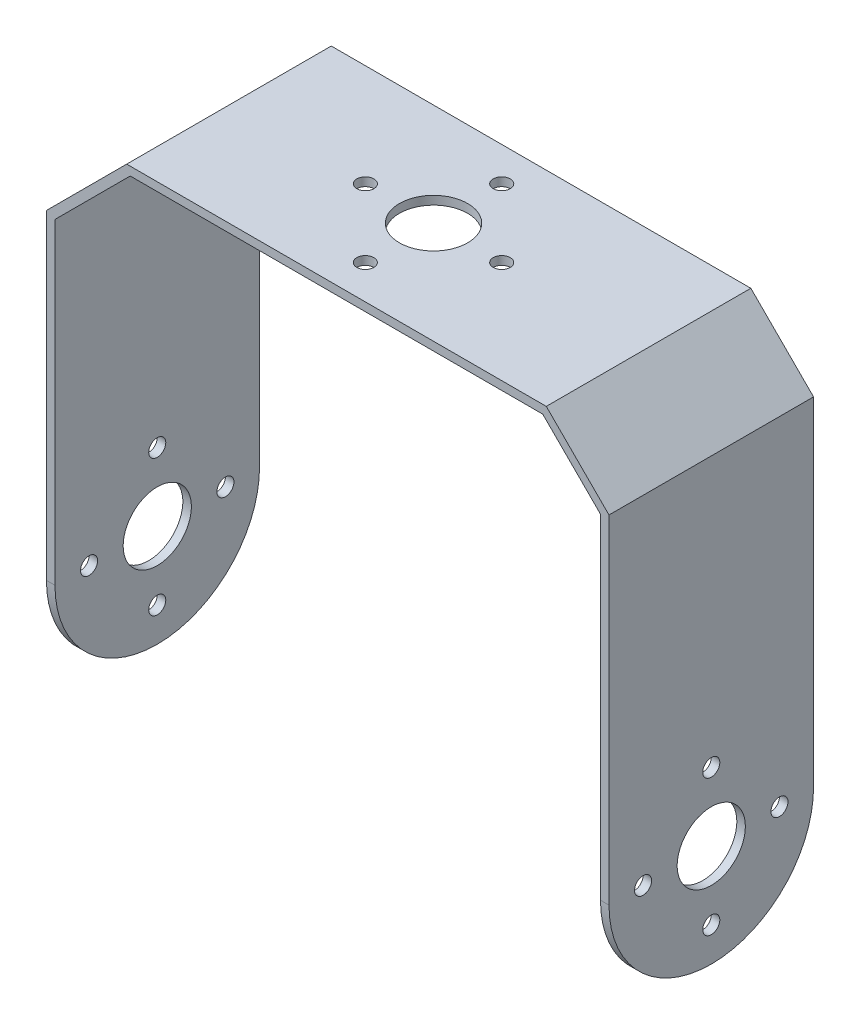
SolidWorks part; units mm, degrees
material "Plain Carbon Steel"
ref_plane "Front Plane" through (0, 0, 0) normal (0, 0, 1) x (1, 0, 0)
ref_plane "Top Plane" through (0, 0, 0) normal (0, 1, 0) x (1, 0, 0)
ref_plane "Right Plane" through (0, 0, 0) normal (1, 0, 0) x (0, 0, -1)
sketch "Sketch1" plane through (0, 0, 0) normal (0, 0, 1) x (1, 0, 0)
  line L0 (18.7066, 0.2468) -> (18.7066, -50.9816)
  line L1 (18.7066, 0.2468) -> (11.935, 7.0184)
  line L2 (-36.465, 7.0184) -> (11.935, 7.0184)
  line L3 (19.7066, 0.661) -> (19.7066, -50.9816)
  line L4 (-45.2934, -1.8101) -> (-36.465, 7.0184)
  line L5 (-45.2934, -1.8101) -> (-45.2934, -50.9816)
  line L6 (19.7066, 0.661) -> (12.3493, 8.0184)
  line L7 (-36.8792, 8.0184) -> (12.3493, 8.0184)
  line L8 (-46.2934, -1.3959) -> (-36.8792, 8.0184)
  line L9 (-46.2934, -1.3959) -> (-46.2934, -50.9816)
  line L10 (-46.2934, -50.9816) -> (-45.2934, -50.9816)
  line L11 (19.7066, -50.9816) -> (18.7066, -50.9816)
  dimension "D1" = 1
extrude "Boss-Extrude1" add sketch "Sketch1" along normal blind 24
sketch "Sketch5" plane through (-46.2934, 0, 0) normal (-1, 0, 0) x (0, 0, 1)
  line L1 (12, -38.9816) -> (20, -38.9816)
  line L2 (0, -1.3959) -> (0, -50.9816) construction
  line L3 (24, -50.9816) -> (0, -50.9816) construction
  circle A0 centre (12, -38.9816) radius 4
  circle A1 centre (20, -38.9816) radius 1
  circle A2 centre (12, -46.9816) radius 1
  circle A3 centre (4, -38.9816) radius 1
  circle A4 centre (12, -30.9816) radius 1
  point P17 (12, -38.9816)
  dimension "D1" = 12
  dimension "D3" = 8
  dimension "D2" = 12
  dimension "D4" = 4
extrude "Cut-Extrude3" cut sketch "Sketch5" against normal blind 1 contours A0 | A4 | A2 | A3 | A1 region at (-46.2934, -38.9816, 8.1131)
sketch "Sketch6" plane through (19.7066, 0, 0) normal (1, 0, 0) x (0, 0, -1)
  line L0 (-12, -38.9816) -> (-4, -38.9816)
  line L1 (-24, -50.9816) -> (0, -50.9816) construction
  line L2 (-24, -50.9816) -> (-24, 0.661) construction
  circle A0 centre (-12, -38.9816) radius 4
  circle A1 centre (-4, -38.9816) radius 1
  circle A2 centre (-12, -46.9816) radius 1
  circle A3 centre (-12, -38.9816) radius 4
  circle A4 centre (-20, -38.9816) radius 1
  circle A5 centre (-12, -38.9816) radius 4
  circle A6 centre (-12, -30.9816) radius 1
  circle A7 centre (-12, -38.9816) radius 4
  point P19 (-12, -38.9816)
  dimension "D1" = 12
  dimension "D2" = 12
  dimension "D3" = 8
  dimension "D4" = 4
extrude "Cut-Extrude4" cut sketch "Sketch6" against normal blind 1 contours A1 | A6 | A4 | A0 | A2
sketch "Sketch7" plane through (0, 8.0184, 0) normal (0, 1, 0) x (1, 0, 0)
  line L1 (-12.8792, -12) -> (-12.8792, -20)
  line L2 (-36.8792, -24) -> (-36.8792, 0) construction
  line L3 (12.3493, 0) -> (-36.8792, 0) construction
  circle A0 centre (-12.8792, -12) radius 4
  circle A1 centre (-12.8792, -20) radius 1
  circle A2 centre (-20.8792, -12) radius 1
  circle A3 centre (-12.8792, -4) radius 1
  circle A4 centre (-4.8792, -12) radius 1
  point P17 (-12.8792, -12)
  dimension "D1" = 8
  dimension "D2" = 24
  dimension "D3" = 12
  dimension "D4" = 4
extrude "Cut-Extrude5" cut sketch "Sketch7" against normal blind 1 contours A3 | A1 | A2 | A4 | A0
fillet "Fillet1" radius 12 4 edges at (19.2066, -50.9816, 24) (19.2066, -50.9816, 0) (-45.7934, -50.9816, 24) (-45.7934, -50.9816, 0)
